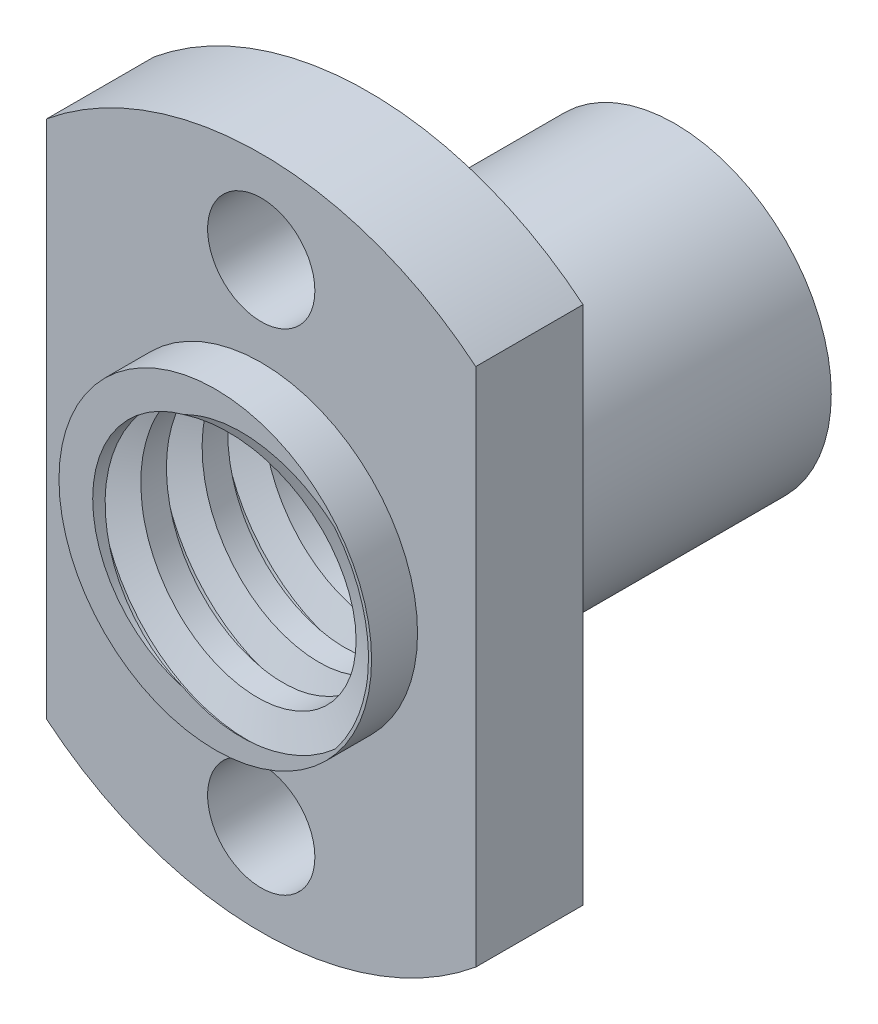
SolidWorks part; units mm, degrees
material "Brass"
ref_plane "Front Plane" through (0, 0, 0) normal (0, 0, 1) x (1, 0, 0)
ref_plane "Top Plane" through (0, 0, 0) normal (0, 1, 0) x (1, 0, 0)
ref_plane "Right Plane" through (0, 0, 0) normal (1, 0, 0) x (0, 0, -1)
sketch "Sketch1" plane through (0, 0, 0) normal (0, 0, 1) x (1, 0, 0)
  line L0 (-7, -8.4853) -> (-7, 8.4853)
  line L1 (7, -8.4853) -> (7, 8.4853)
  arc A0 (7, 8.4853) -> (-7, 8.4853) centre (0, 0) ccw
  circle A1 centre (0, 0) radius 5.1
  circle A2 centre (0, 0) radius 8 construction
  circle A3 centre (0, 8) radius 1.75
  arc A4 (-7, -8.4853) -> (7, -8.4853) centre (0, 0) ccw
  circle A5 centre (0, -8) radius 1.75
  circle A7 centre (-8, 0) radius 1.75 [skipped]
  circle A8 centre (8, 0) radius 1.75 [skipped]
  point P16 (0, 0)
  dimension "D1" = 22
  dimension "D2" = 10.2
  dimension "D3" = 16
  dimension "D4" = 3.5
  dimension "D6" = 7
  dimension "D7" = 7
  dimension "D5" = 4
extrude "Boss-Extrude1" add sketch "Sketch1" against normal blind 3.5
sketch "Sketch2" plane through (0, 0, 0) normal (0, 0, 1) x (1, 0, 0)
  circle A0 centre (0, 0) radius 5.1
  circle A1 centre (0, 0) radius 4
  dimension "D1" = 8
extrude "Boss-Extrude2" add sketch "Sketch2" along normal blind 1.5 and the other way blind 13.5
sketch "Sketch3" plane through (0, 0, 1.5) normal (0, 0, 1) x (1, 0, 0)
  circle A0 centre (0, 0) radius 4
curve "Helix/Spiral1" pitch 2 height 15 radius 4 centre (0, 0, 1.5) axis (0, 0, -1) start towards (1, 0, 0)
sketch "Sketch4" plane through (0, 0, 0) normal (0, 1, 0) x (1, 0, 0)
  line L0 (3, -0.55) -> (3, -2.45)
  line L1 (3, -2.45) -> (5, -1.7146)
  line L2 (5, -1.7146) -> (5, -1.2854)
  line L3 (5, -1.2854) -> (3, -0.55)
  line L4 (3, -1.5) -> (5, -1.5)
  point P6 (4, -1.5)
  dimension "D1" = 1.9
  dimension "D2" = 2
  dimension "D3" = 69.811
sweep "Cut-Sweep1" cut profiles "Sketch4" path "Helix/Spiral1" align with end faces yes
